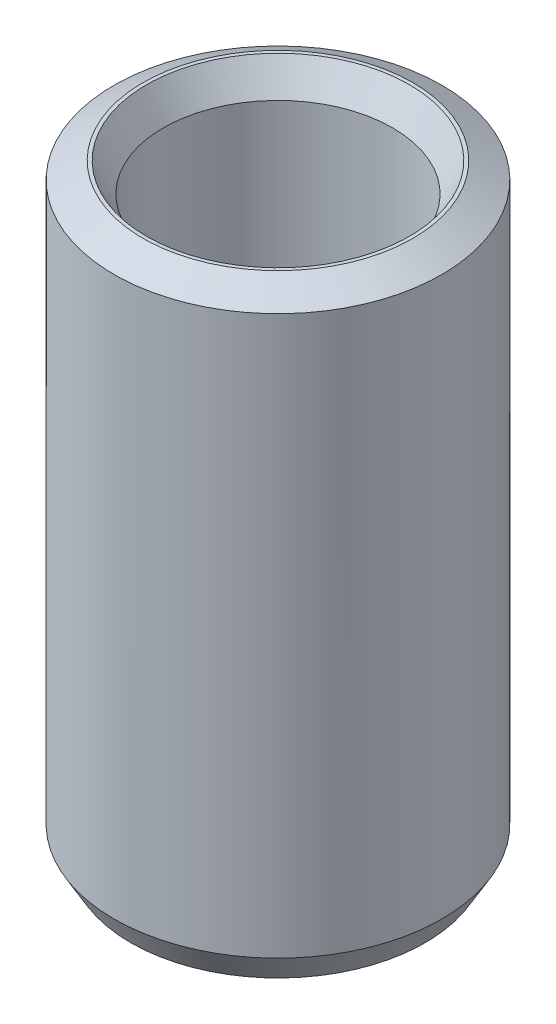
SolidWorks part; units mm, degrees
ref_plane "Front Plane" through (0, 0, 0) normal (0, 0, 1) x (1, 0, 0)
ref_plane "Top Plane" through (0, 0, 0) normal (0, 1, 0) x (1, 0, 0)
ref_plane "Right Plane" through (0, 0, 0) normal (1, 0, 0) x (0, 0, -1)
sketch "Sketch1" plane through (0, 0, 0) normal (0, 1, 0) x (1, 0, 0)
  circle A0 centre (0, 0) radius 30
  dimension "SLEEVE_OD" = 60
extrude "Boss-Extrude1" add sketch "Sketch1" along normal blind 110.5044
sketch "Sketch2" plane through (0, 0, 0) normal (0, 1, 0) x (1, 0, 0)
  circle A0 centre (0, 0) radius 20.9807
  dimension "BORE_D" = 41.9614
extrude "Cut-Extrude1" cut sketch "Sketch2" along normal through all
chamfer "Chamfer1" distance 3.0661 angle 60 4 edges at (0, 110.5044, 20.9807) (0, 0, 20.9807) (0, 0, 30) (0, 110.5044, 30) first distance on face at (0, 110.5044, 20.9807) first distance on face at (0, 0, 20.9807) first distance on face at (0, 110.5044, 30)
